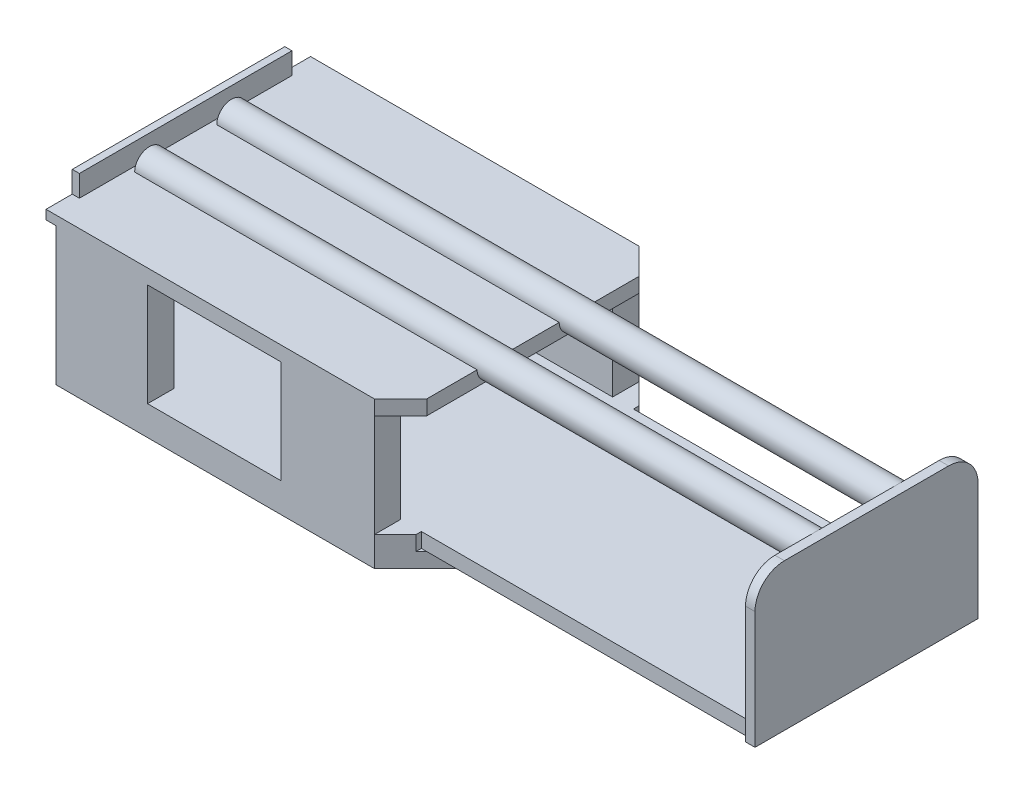
SolidWorks part; units mm, degrees
note: The reader was unsure of these and kept them because the rebuilt part matched: shared geometry of "Sketch1<4>", "Sketch1<5>".
ref_plane "Front Plane" through (0, 0, 0) normal (0, 0, 1) x (1, 0, 0)
ref_plane "Top Plane" through (0, 0, 0) normal (0, 1, 0) x (1, 0, 0)
ref_plane "Right Plane" through (0, 0, 0) normal (1, 0, 0) x (0, 0, -1)
sketch "Sketch1" plane through (0, 0, 0) normal (0, 1, 0) x (1, 0, 0)
  line L0 (293.0219, 210.6395) -> (293.0219, 17.9605) construction
  line L1 (0, 0) -> (275.0614, 0)
  line L2 (0, 0) -> (0, 228.6)
  line L4 (586.0437, 17.9605) -> (586.0437, 210.6395)
  line L5 (586.0437, 210.6395) -> (293.0219, 210.6395)
  line L6 (0, 114.3) -> (577.8656, 114.3) construction
  line L7 (293.0219, 17.9605) -> (275.0614, 0)
  line L8 (293.0219, 210.6395) -> (275.0614, 228.6)
  line L9 (586.0437, 114.3) -> (586.0437, 17.9605)
  line L10 (586.0437, 17.9605) -> (293.0219, 17.9605)
  line L11 (586.0437, 17.9605) -> (586.0437, 114.3)
  line L12 (0, 228.6) -> (275.0614, 228.6)
  line L13 (293.0219, 22.6748) -> (577.8656, 22.6748)
  line L14 (0, 228.6) -> (79.1426, 228.6)
  line L15 (0, 228.6) -> (0, 205.9252)
  line L16 (0, 205.9252) -> (79.1426, 205.9252)
  line L17 (79.1426, 228.6) -> (79.1426, 205.9252)
  line L18 (275.0614, 228.6) -> (194.4159, 228.6)
  line L19 (275.0614, 228.6) -> (275.0614, 205.9252)
  line L20 (275.0614, 205.9252) -> (194.4159, 205.9252)
  line L21 (194.4159, 228.6) -> (194.4159, 205.9252)
  line L22 (293.0219, 210.6395) -> (586.0437, 210.6395)
  line L23 (293.0219, 210.6395) -> (293.0219, 205.9252)
  line L24 (293.0219, 205.9252) -> (577.8656, 205.9252)
  line L25 (586.0437, 210.6395) -> (586.0437, 205.9252)
  line L27 (577.8656, 205.9252) -> (577.8656, 114.3)
  line L29 (586.0437, 205.9252) -> (586.0437, 114.3)
  line L30 (586.0437, 17.9605) -> (586.0437, 22.6748)
  line L31 (293.0219, 17.9605) -> (586.0437, 17.9605)
  line L32 (293.0219, 17.9605) -> (293.0219, 22.6748)
  line L33 (275.0614, 22.6748) -> (194.4159, 22.6748)
  line L34 (194.4159, 0) -> (194.4159, 22.6748)
  line L35 (275.0614, 0) -> (194.4159, 0)
  line L36 (275.0614, 0) -> (275.0614, 22.6748)
  line L37 (0, 22.6748) -> (79.1426, 22.6748)
  line L38 (79.1426, 0) -> (79.1426, 22.6748)
  line L39 (0, 0) -> (79.1426, 0)
  line L40 (0, 0) -> (0, 22.6748)
  line L42 (586.0437, 17.9605) -> (577.8656, 17.9605)
  line L43 (586.0437, 17.9605) -> (586.0437, 210.6395)
  line L44 (586.0437, 210.6395) -> (577.8656, 210.6395)
  line L45 (577.8656, 17.9605) -> (577.8656, 210.6395)
extrude "Boss-Extrude1" add sketch "Sketch1" along normal blind 12.7 contours L13 L45 L27 L24 L23 L8 L19 L20 L21 L12 L17 L16 L2 L37 L38 L1 L34 L33 L36 L7 L32
extrude "Boss-Extrude2" add sketch "Sketch1<4>" along normal blind 127 contours L45 L10 L4 L11 L5 L27
sketch "Sketch1<4>" plane through (0, 0, 0) normal (0, 1, 0) x (1, 0, 0) same geometry as "Sketch1"
fillet "Fillet1" radius 25.4 1 edges at (581.9547, 127, -17.9605)
fillet "Fillet2" radius 25.4 1 edges at (581.9547, 127, -210.6395)
extrude "Boss-Extrude3" add sketch "Sketch1<5>" along normal blind 101.6 contours L12 L21 L20 L19 | L17 L12 L2 L16 | L1 L36 L33 L34 | L1 L38 L37 L2
sketch "Sketch1<5>" plane through (0, 0, 0) normal (0, 1, 0) x (1, 0, 0) same geometry as "Sketch1"
sketch "Sketch2" plane through (0, 0, 0) normal (0, -1, 0) x (1, 0, 0)
  line L0 (275.0614, 0) -> (373.8321, -98.7708)
  line L1 (0, 0) -> (275.0614, 0)
  line L2 (0, 0) -> (0, -228.6)
  line L3 (0, -228.6) -> (275.0614, -228.6)
  line L5 (373.8321, -129.8292) -> (275.0614, -228.6)
  line L6 (373.8321, -129.8292) -> (373.8321, -98.7708)
extrude "Boss-Extrude4" add sketch "Sketch2" along normal blind 12.7
sketch "Sketch3" [suppressed] plane through (0, -12.7, 0) normal (0, -1, 0) x (1, 0, 0)
  line L0 (0, -114.3) -> (373.8321, -114.3) construction
  line L1 (0, 0) -> (0, -228.6) construction
  line L2 (373.8321, -129.8292) -> (373.8321, -98.7708) construction
  circle A0 centre (186.9161, -114.3) radius 114.3
sketch "Sketch4" plane through (0, 101.6, 0) normal (0, 1, 0) x (1, 0, 0)
  line L0 (275.0614, 228.6) -> (297.7362, 205.9252)
  line L1 (0, 228.6) -> (275.0614, 228.6)
  line L2 (0, 228.6) -> (0, 0)
  line L3 (0, 0) -> (275.0614, 0)
  line L5 (297.7362, 205.9252) -> (297.7362, 22.6748)
  line L6 (293.0219, 22.6748) -> (577.8656, 22.6748) construction
  line L7 (297.7362, 22.6748) -> (275.0614, 0)
extrude "Boss-Extrude5" add sketch "Sketch4" along normal blind 12.7
sketch "Sketch5" plane through (586.0437, 0, 0) normal (1, 0, 0) x (0, 0, -1)
  line L0 (43.3605, 114.3) -> (185.2395, 114.3) construction
  line L3 (185.2395, 114.3) -> (114.3, 114.3) construction
  line L4 (210.6395, 101.6) -> (185.2395, 101.6) construction
  line L5 (114.3, 114.3) -> (114.3, 127) construction
  line L6 (43.3605, 127) -> (43.3605, 101.6) construction
  line L7 (43.3605, 101.6) -> (17.9605, 101.6) construction
  line L8 (185.2395, 127) -> (185.2395, 101.6) construction
  line L9 (43.3605, 127) -> (185.2395, 127) construction
  line L10 (43.3605, 101.6) -> (114.3, 127) construction
  line L11 (114.3, 127) -> (185.2395, 101.6) construction
  circle A0 centre (78.8303, 114.3) radius 12.7
  circle A1 centre (149.7697, 114.3) radius 12.7
extrude "Boss-Extrude7" add sketch "Sketch5" against normal blind 584.2
sketch "Sketch6" [suppressed] plane through (0, 114.3, 0) normal (0, 1, 0) x (1, 0, 0)
  line L1 (297.7362, 205.9252) -> (0, 205.9252)
  line L2 (297.7362, 205.9252) -> (297.7362, 22.6748)
  line L3 (297.7362, 22.6748) -> (0, 22.6748)
  line L4 (0, 205.9252) -> (0, 22.6748)
sketch "Sketch7" plane through (0, 0, 0) normal (-1, 0, 0) x (0, 0, 1)
  line L0 (0, 114.3) -> (0, -12.7) construction
  line L1 (-228.6, 114.3) -> (0, 114.3)
  line L2 (-228.6, 114.3) -> (-228.6, 106.3471)
  line L3 (-228.6, 106.3471) -> (0, 106.3471)
  line L4 (0, 114.3) -> (0, 106.3471)
extrude "Boss-Extrude8" add sketch "Sketch7" along normal blind 8.636
sketch "Sketch8" plane through (0, 114.3, 0) normal (0, 1, 0) x (1, 0, 0)
  line L0 (-8.636, 0) -> (-8.636, 228.6) construction
  line L1 (-8.636, 206.3488) -> (-2.474, 206.3488)
  line L2 (-8.636, 206.3488) -> (-8.636, 22.6748)
  line L3 (-8.636, 22.6748) -> (-2.474, 22.6748)
  line L4 (-2.474, 206.3488) -> (-2.474, 22.6748)
extrude "Boss-Extrude9" add sketch "Sketch8" along normal blind 18.542
sketch "Sketch9" plane through (0, -12.7, 0) normal (0, -1, 0) x (1, 0, 0)
  line L0 (275.0614, -114.3) -> (-8.636, -114.3) construction
  line L1 (275.0614, -228.6) -> (-8.636, -228.6) construction
  line L2 (275.0614, -228.6) -> (275.0614, 0) construction
  line L3 (275.0614, 0) -> (-8.636, 0) construction
  line L4 (-8.636, -228.6) -> (-8.636, 0) construction
  circle A0 centre (133.2127, -114.3) radius 50.8 construction
